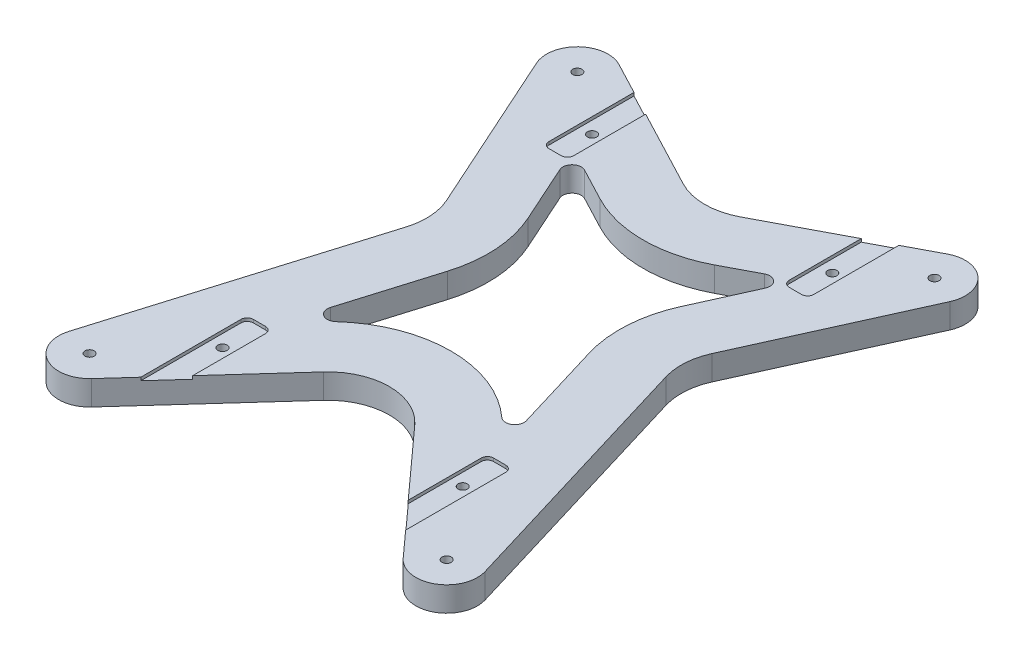
SolidWorks part; units mm, degrees
material "PMMA"
ref_plane "Front Plane" through (0, 0, 0) normal (0, 0, 1) x (1, 0, 0)
ref_plane "Top Plane" through (0, 0, 0) normal (0, 1, 0) x (1, 0, 0)
ref_plane "Right Plane" through (0, 0, 0) normal (1, 0, 0) x (0, 0, -1)
sketch "Sketch1" plane through (0, 0, 0) normal (0, 1, 0) x (1, 0, 0)
  line L0 (-53.328, 88.0466) -> (0, 60)
  line L1 (0, 60) -> (53.328, 88.0466)
  line L2 (67.0985, 75.0847) -> (40, 15)
  line L3 (40, 15) -> (67.5563, -76.3067)
  line L4 (50.5665, -85.9041) -> (0, -30)
  line L5 (0, -30) -> (-50.5665, -85.9041)
  line L6 (-67.5563, -76.3067) -> (-40, 15)
  line L7 (-40, 15) -> (-67.0985, 75.0847)
  line L8 (-68.5894, 68.5894) -> (68.5894, -68.5894) construction
  line L9 (-42, 75) -> (-36, 75) construction
  line L10 (-42, 75) -> (-42, 55) construction
  line L11 (-42, 55) -> (-36, 55) construction
  line L12 (-36, 75) -> (-36, 55) construction
  line L13 (-42, 75) -> (-36, 55) construction
  line L14 (-42, 55) -> (-36, 75) construction
  line L15 (36, 75) -> (42, 75) construction
  line L16 (36, 75) -> (36, 55) construction
  line L17 (36, 55) -> (42, 55) construction
  line L18 (42, 75) -> (42, 55) construction
  line L19 (36, 75) -> (42, 55) construction
  line L20 (36, 55) -> (42, 75) construction
  line L21 (36, -45) -> (42, -45) construction
  line L22 (36, -45) -> (36, -65) construction
  line L23 (36, -65) -> (42, -65) construction
  line L24 (42, -45) -> (42, -65) construction
  line L25 (36, -45) -> (42, -65) construction
  line L26 (36, -65) -> (42, -45) construction
  line L27 (-42, -45) -> (-36, -45) construction
  line L28 (-42, -45) -> (-42, -65) construction
  line L29 (-42, -65) -> (-36, -65) construction
  line L30 (-36, -45) -> (-36, -65) construction
  line L31 (-42, -45) -> (-36, -65) construction
  line L32 (-42, -65) -> (-36, -45) construction
  line L33 (97, 40.1787) -> (40.1787, 97) construction
  line L34 (40.1787, 97) -> (-40.1787, 97) construction
  line L35 (-40.1787, 97) -> (-97, 40.1787) construction
  line L36 (-97, 40.1787) -> (-97, -40.1787) construction
  line L37 (-97, -40.1787) -> (-40.1787, -97) construction
  line L38 (-40.1787, -97) -> (40.1787, -97) construction
  line L39 (40.1787, -97) -> (97, -40.1787) construction
  line L40 (97, -40.1787) -> (97, 40.1787) construction
  line L41 (68.5894, 68.5894) -> (-68.5894, -68.5894) construction
  circle A0 centre (-57.9828, 79.196) radius 1.5
  circle A1 centre (57.9828, 79.196) radius 1.5
  circle A2 centre (-57.9828, -79.196) radius 1.5
  circle A3 centre (57.9828, -79.196) radius 1.5
  arc A4 (-53.328, 88.0466) -> (-67.0985, 75.0847) centre (-57.9828, 79.196) ccw
  arc A5 (53.328, 88.0466) -> (67.0985, 75.0847) centre (57.9828, 79.196) cw
  arc A6 (-67.5563, -76.3067) -> (-50.5665, -85.9041) centre (-57.9828, -79.196) ccw
  arc A7 (67.5563, -76.3067) -> (50.5665, -85.9041) centre (57.9828, -79.196) cw
  circle A8 centre (0, 0) radius 97 construction
  circle A9 centre (-39, 65) radius 1.5
  circle A10 centre (39, 65) radius 1.5
  circle A11 centre (39, -55) radius 1.5
  circle A12 centre (-39, -55) radius 1.5
  ellipse E0 centre (0, 15) end of major axis (0, 60) minor radius 40 construction
  dimension "D5" = 3
  dimension "D6" = 45
  dimension "D7" = 10
  dimension "D12" = 3
  dimension "D3" = 15
  dimension "D4" = 15
  dimension "D8" = 120
  dimension "D9" = 78
  dimension "D10" = 15
  dimension "D11" = 55
  dimension "D13" = 40
  dimension "D14" = 39
  dimension "D15" = 20
  dimension "D16" = 6
  dimension "D17" = 97
  dimension "D18" = 15
extrude "Boss-Extrude1" add sketch "Sketch1" along normal blind 8
fillet "Fillet1" radius 20 4 edges at (0, 4, -60) (-40, 4, -15) (0, 4, 30) (40, 4, -15)
sketch "Sketch2" plane through (0, 8, 0) normal (0, 1, 0) x (1, 0, 0)
  line L44 (-36.9213, 56.8206) -> (-24.8484, 30.0516)
  line L45 (-23.0175, 2.0495) -> (-35.5552, -39.4938)
  line L46 (-35.5552, -39.4938) -> (-29.665, -32.9818)
  line L47 (29.665, -32.9818) -> (35.5552, -39.4938)
  line L48 (35.5552, -39.4938) -> (23.0175, 2.0495)
  line L49 (24.8484, 30.0516) -> (36.9213, 56.8206)
  line L50 (36.9213, 56.8206) -> (18.619, 47.1949)
  line L51 (-18.619, 47.1949) -> (-36.9213, 56.8206)
  line L52 (-36.9213, 56.8206) -> (-24.8484, 30.0516)
  line L53 (-23.0175, 2.0495) -> (-35.5552, -39.4938)
  line L54 (-35.5552, -39.4938) -> (-29.665, -32.9818)
  line L55 (29.665, -32.9818) -> (35.5552, -39.4938)
  line L56 (35.5552, -39.4938) -> (23.0175, 2.0495)
  line L57 (24.8484, 30.0516) -> (36.9213, 56.8206)
  line L58 (36.9213, 56.8206) -> (18.619, 47.1949)
  line L59 (-18.619, 47.1949) -> (-36.9213, 56.8206)
  arc A40 (-23.0175, 2.0495) -> (-24.8484, 30.0516) centre (-61.3115, 13.6066) ccw
  arc A41 (29.665, -32.9818) -> (-29.665, -32.9818) centre (0, -59.8145) ccw
  arc A42 (24.8484, 30.0516) -> (23.0175, 2.0495) centre (61.3115, 13.6066) ccw
  arc A43 (-18.619, 47.1949) -> (18.619, 47.1949) centre (0, 82.5973) ccw
  arc A44 (-23.0175, 2.0495) -> (-24.8484, 30.0516) centre (-61.3115, 13.6066) ccw
  arc A45 (29.665, -32.9818) -> (-29.665, -32.9818) centre (0, -59.8145) ccw
  arc A46 (24.8484, 30.0516) -> (23.0175, 2.0495) centre (61.3115, 13.6066) ccw
  arc A47 (-18.619, 47.1949) -> (18.619, 47.1949) centre (0, 82.5973) ccw
  dimension "D1" = 20
extrude "Cut-Extrude1" cut sketch "Sketch2" against normal up to next
fillet "Fillet2" radius 3 4 edges at (35.5552, 4, 39.4938) (-35.5552, 4, 39.4938) (36.9213, 4, -56.8206) (-36.9213, 4, -56.8206)
sketch "Sketch4" plane through (0, 8, 0) normal (0, 1, 0) x (1, 0, 0)
  line L0 (-9.3095, 64.8961) -> (-53.328, 88.0466) construction
  line L1 (-37, 53) -> (-41, 53)
  line L2 (-35, 55) -> (-35, 82.6148)
  line L3 (-35, 82.6148) -> (-43, 82.6148)
  line L4 (-43, 55) -> (-43, 82.6148)
  line L5 (53.328, 88.0466) -> (9.3095, 64.8961) construction
  line L6 (37, 53) -> (41, 53)
  line L7 (35, 55) -> (35, 82.6148)
  line L8 (35, 82.6148) -> (43, 82.6148)
  line L9 (43, 55) -> (43, 82.6148)
  line L10 (-50.5665, -85.9041) -> (-14.8325, -46.3981) construction
  line L11 (-37, -43) -> (-41, -43)
  line L12 (-35, -45) -> (-35, -77.5389)
  line L13 (-35, -77.5389) -> (-43, -77.5389)
  line L14 (-43, -45) -> (-43, -77.5389)
  line L15 (14.8325, -46.3981) -> (50.5665, -85.9041) construction
  line L16 (37, -43) -> (41, -43)
  line L17 (35, -45) -> (35, -77.5389)
  line L18 (35, -77.5389) -> (43, -77.5389)
  line L19 (43, -45) -> (43, -77.5389)
  circle A0 centre (-39, -55) radius 1.5 construction
  circle A1 centre (-39, 65) radius 1.5 construction
  circle A2 centre (39, -55) radius 1.5 construction
  arc A3 (41, -43) -> (43, -45) centre (41, -45) cw
  arc A4 (37, -43) -> (35, -45) centre (37, -45) ccw
  arc A5 (-41, -43) -> (-43, -45) centre (-41, -45) ccw
  arc A6 (-37, -43) -> (-35, -45) centre (-37, -45) cw
  arc A7 (41, 53) -> (43, 55) centre (41, 55) ccw
  arc A8 (37, 53) -> (35, 55) centre (37, 55) cw
  arc A9 (-37, 53) -> (-35, 55) centre (-37, 55) ccw
  arc A10 (-41, 53) -> (-43, 55) centre (-41, 55) cw
  dimension "D2" = 4
  dimension "D4" = 12
  dimension "D5" = 4
  dimension "D6" = 2
  dimension "D1" = 8
  dimension "D3" = 12
extrude "Cut-Extrude2" cut sketch "Sketch4" against normal blind 1
equation "\"D14@Sketch1\"=\"D9@Sketch1\"/2"
